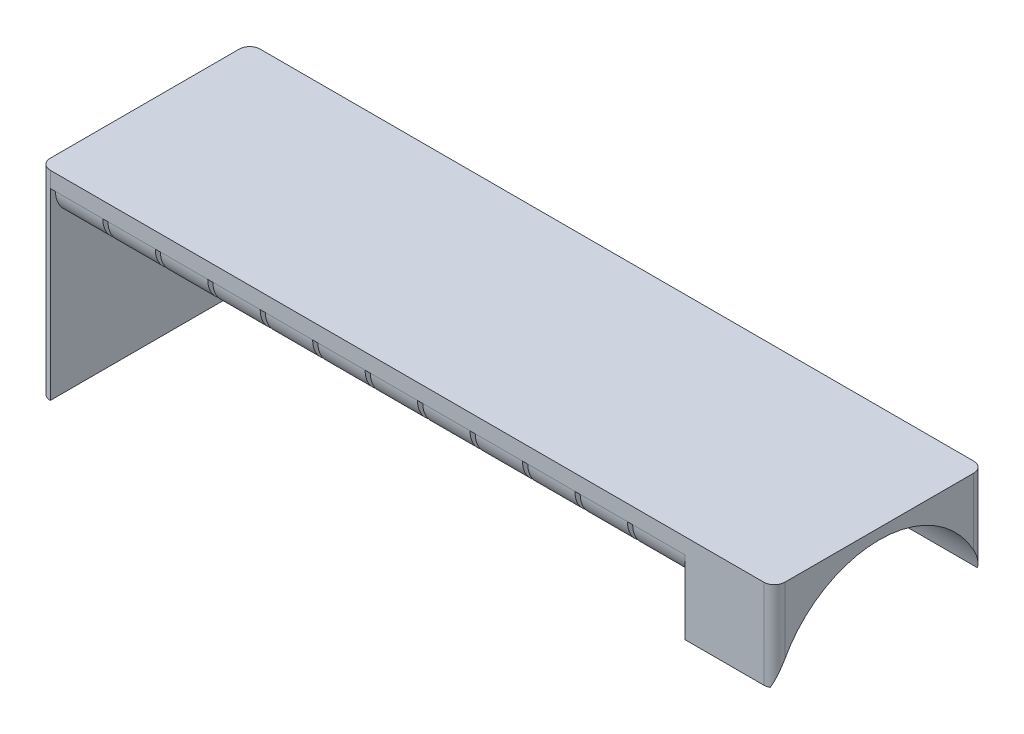
SolidWorks part; units mm, degrees
ref_plane "Front Plane" through (0, 0, 0) normal (0, 0, 1) x (1, 0, 0)
ref_plane "Top Plane" through (0, 0, 0) normal (0, 1, 0) x (1, 0, 0)
ref_plane "Right Plane" through (0, 0, 0) normal (1, 0, 0) x (0, 0, -1)
sketch "Sketch1" plane through (0, 0, 0) normal (0, 1, 0) x (1, 0, 0)
  line L1 (-70, 20) -> (70, 20)
  line L2 (-70, 20) -> (-70, -20)
  line L3 (-70, -20) -> (70, -20)
  line L4 (70, 20) -> (70, -20)
  line L5 (-70, 20) -> (70, -20) construction
  line L6 (-70, -20) -> (70, 20) construction
  line L7 (-70, 20) -> (-68, 20)
  line L8 (-70, 20) -> (-70, -20)
  line L9 (-70, -20) -> (-68, -20)
  line L10 (-68, 20) -> (-68, -20)
  line L11 (-70, 20) -> (-68, -20) construction
  line L12 (-70, -20) -> (-68, 20) construction
  line L13 (70, 20) -> (55, 20)
  line L14 (70, 20) -> (70, -20)
  line L15 (70, -20) -> (55, -20)
  line L16 (55, 20) -> (55, -20)
  line L17 (70, 20) -> (55, -20) construction
  line L18 (70, -20) -> (55, 20) construction
  point P0 (0, 0)
  point P8 (-69, 0)
  point P11 (62.5, 0)
  dimension "D1" = 140
  dimension "D2" = 40
  dimension "D3" = 2
  dimension "D4" = 15
extrude "Boss-Extrude1" add sketch "Sketch1" along normal blind 8 contours L16 L1 L10 L3 | L1 L16 L3 L4 | L10 L1 L2 L3 region at (-69, 0, 0) region at (-6.5, 0, 0) region at (62.5, 0, 0)
extrude "Boss-Extrude2" add sketch "Sketch1<3>" against normal blind 9 contours L1 L16 L3 L4 region at (62.5, 0, 0)
sketch "Sketch1<3>" plane through (0, 0, 0) normal (0, 1, 0) x (1, 0, 0) same geometry as "Sketch1"
sketch "Sketch2" plane through (55, 0, 0) normal (-1, 0, 0) x (0, 0, 1)
  line L0 (-20, 0) -> (20, 0) construction
  line L1 (9.125, 0) -> (-9.125, 0)
  line L2 (9.125, 0) -> (9.125, -9)
  line L3 (9.125, -9) -> (-9.125, -9)
  line L4 (-9.125, 0) -> (-9.125, -9)
  line L5 (9.125, 0) -> (-9.125, -9) construction
  line L6 (9.125, -9) -> (-9.125, 0) construction
  line L7 (-20, -9) -> (-20, 0) construction
  line L8 (9.125, -9) -> (8.525, -9)
  line L9 (9.125, -9) -> (9.125, 0)
  line L10 (9.125, 0) -> (8.525, 0)
  line L11 (8.525, -9) -> (8.525, 0)
  line L12 (9.125, -9) -> (8.525, 0) construction
  line L13 (9.125, 0) -> (8.525, -9) construction
  line L14 (-9.125, -9) -> (-8.525, -9)
  line L15 (-9.125, -9) -> (-9.125, 0)
  line L16 (-9.125, 0) -> (-8.525, 0)
  line L17 (-8.525, -9) -> (-8.525, 0)
  line L18 (-9.125, -9) -> (-8.525, 0) construction
  line L19 (-9.125, 0) -> (-8.525, -9) construction
  line L20 (8.525, -0.6) -> (-8.525, -0.6)
  line L21 (8.525, -0.6) -> (8.525, 0)
  line L22 (8.525, 0) -> (-8.525, 0)
  line L23 (-8.525, -0.6) -> (-8.525, 0)
  line L24 (8.525, -0.6) -> (-8.525, 0) construction
  line L25 (8.525, 0) -> (-8.525, -0.6) construction
  line L26 (-9.125, -9) -> (-20, -9)
  line L27 (-9.125, -9) -> (-9.125, 0)
  line L28 (-9.125, 0) -> (-20, 0)
  line L29 (-20, -9) -> (-20, 0)
  line L30 (-9.125, -9) -> (-20, 0) construction
  line L31 (-9.125, 0) -> (-20, -9) construction
  line L33 (9.125, -9) -> (20, -9)
  line L34 (9.125, -9) -> (9.125, 0)
  line L35 (9.125, 0) -> (20, 0)
  line L36 (20, -9) -> (20, 0)
  line L37 (9.125, -9) -> (20, 0) construction
  line L38 (9.125, 0) -> (20, -9) construction
  point P4 (0, -4.5)
  point P7 (0, 0)
  point P11 (8.825, -4.5)
  point P14 (-8.825, -4.5)
  point P18 (0, -0.3)
  point P20 (-14.5625, -4.5)
  point P25 (14.5625, -4.5)
  line M3 (20, 0) -> (-20, 0)
  line M4 (-20, 0) -> (-20, -9)
  line M6 (20, -9) -> (20, 0)
  dimension "D1" = 18.25
  dimension "D2" = 9
  dimension "D3" = 0.6
  dimension "D4" = 0.6
  dimension "D5" = 0.6
extrude "Boss-Extrude3" add sketch "Sketch2" along normal blind 1 contours L2 L33 M6 M3 | L26 L4 M3 M4 region at (55, -4.5, 14.5625) region at (55, -4.5, -14.5625)
extrude "Boss-Extrude4" add sketch "Sketch2<3>" along normal blind 1 from surface contours L11 L3 L2 M3 | L2 L33 M6 M3 | L20 L11 L1 L17 | L3 L17 L4 M3 | L26 L4 M3 M4 region at (55, -4.5, 8.825) region at (55, -4.5, 14.5625) region at (55, -0.3, 0) region at (55, -4.5, -8.825) region at (55, -4.5, -14.5625) starting at face at (54, -4.5, 14.5625)
sketch "Sketch2<3>" plane through (55, 0, 0) normal (-1, 0, 0) x (0, 0, 1) same geometry as "Sketch2"
ref_plane "Plane1" through (51, 0, 0) normal (-1, 0, 0) x (0, 0, 1)
extrude "Boss-Extrude5" add sketch "Sketch1<4>" against normal blind 30 contours L10 L1 L2 L3 region at (-69, 0, 0)
sketch "Sketch1<4>" plane through (0, 0, 0) normal (0, 1, 0) x (1, 0, 0) same geometry as "Sketch1"
sketch "Sketch3" plane through (51, 0, 0) normal (-1, 0, 0) x (0, 0, 1)
  line L0 (0, 0) -> (0, -6.5) construction
  line L1 (11.6554, -3.25) -> (-11.6554, -3.25)
  line L2 (-11.6554, -3.25) -> (-11.6554, 0)
  line L3 (-11.6554, 0) -> (0, 0)
  line L4 (0, 0) -> (11.6554, 0)
  line L5 (-20, 0) -> (20, 0) construction
  line L6 (11.6554, 0) -> (11.6554, -3.25)
  circle A0 centre (0, -6.5) radius 12.1
  point P7 (0, -3.25)
  dimension "D1" = 24.2
  dimension "D2" = 6.5
extrude "Cut-Extrude1" cut sketch "Sketch3" along normal up to surface (119 mm away) contours L1 A0 | L4 L0 L1 A0 | L0 L3 A0 L1 | L4 A0 L3 region at (51, -1.6604, 5.5213) region at (51, -1.6604, -5.5213) region at (51, 2.2914, 0) region at (51, -9.9308, 0) up to face at (-68, -15, 0)
fillet "Fillet1" radius 5 2 edges at (-7.5, 0, 20) (-7.5, 0, -20)
fillet "Fillet2" radius 2 4 edges at (-70, -11, 20) (-70, -11, -20) (70, -0.5, 20) (70, -0.5, -20)
extrude "Boss-Extrude6" add sketch "Sketch3<3>" along normal up to surface and the other way up to surface contours A0 L3 L2 | A0 L6 L4 region at (51, -1.0038, 11.2018) region at (51, -1.0038, -11.2018) up to face at (-68, -5.8089, 0) other way up to face at (53, -2.9271, 0)
sketch "Sketch3<3>" plane through (51, 0, 0) normal (-1, 0, 0) x (0, 0, 1) same geometry as "Sketch3"
fillet "Fillet3" radius 0.5 2 edges at (-7.5, -3.25, -11.6554) (-7.5, -3.25, 11.6554)
fillet "Fillet5" radius 1 1 edges at (51, 0, 0)
ref_plane "sensor plane" through (53, 0, 0) normal (-1, 0, 0) x (0, 0, 1)
ref_plane "S1" through (43, 0, 0) normal (-1, 0, 0) x (0, 0, 1)
sketch "Sketch4" plane through (43, 0, 0) normal (-1, 0, 0) x (0, 0, 1)
  line L0 (20, 5) -> (20, -9) construction
  line L1 (-20, 5) -> (20, 5)
  line L2 (-20, 5) -> (-20, -5)
  line L3 (-20, -5) -> (20, -5)
  line L4 (20, 5) -> (20, -5)
  line L5 (-20, 5) -> (20, -5) construction
  line L6 (-20, -5) -> (20, 5) construction
  line L7 (-18, 8) -> (18, 8) construction
  point P0 (0, 0)
  dimension "D1" = 3
extrude "Cut-Extrude2" cut sketch "Sketch4" along normal blind 1 contours L3 L4 L1 L2
pattern_linear "LPattern1" count 13 spacing 10 along (-1, 0, 0) of "Cut-Extrude2"
sketch "Sketch5" plane through (53, 0, 0) normal (-1, 0, 0) x (0, 0, 1)
  line L0 (0, 0) -> (0, 50000) construction
  circle A0 centre (0, -14.5113) radius 20.5
  point P5 (0, -14.5113)
  dimension "D1" = 41
extrude "Cut-Extrude3" cut sketch "Sketch5" against normal through all
